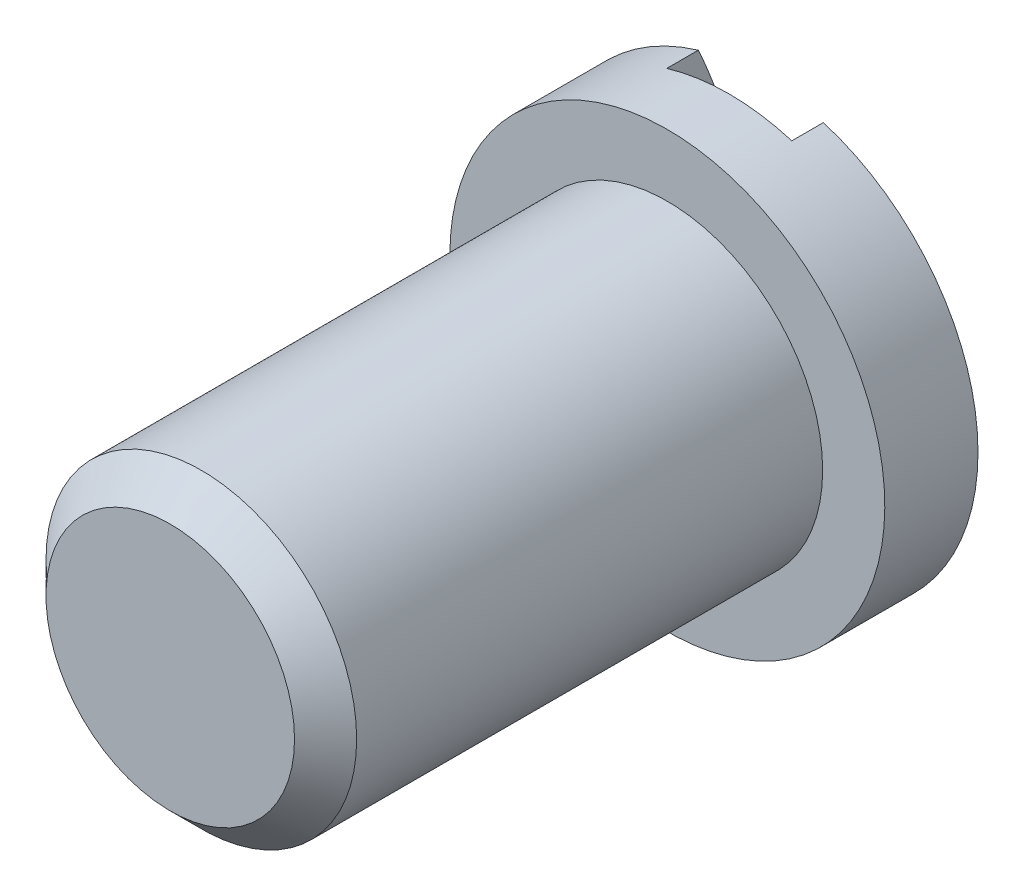
SolidWorks part; units mm, degrees
ref_plane "前视基准面" through (0, 0, 0) normal (0, 0, 1) x (1, 0, 0)
ref_plane "上视基准面" through (0, 0, 0) normal (0, 1, 0) x (1, 0, 0)
ref_plane "右视基准面" through (0, 0, 0) normal (1, 0, 0) x (0, 0, -1)
sketch "草图1" plane through (0, 0, 0) normal (0, 0, 1) x (1, 0, 0)
  circle A0 centre (0, 0) radius 2.5
  dimension "D1" = 5
extrude "凸台-拉伸1" add sketch "草图1" along normal blind 8
cosmetic thread "装饰螺纹线1" parameters "D1"=7.5, "D2"=4
chamfer "倒角2" distance 0.5 angle 45 1 edges at (2.5, 0, 8)
sketch "草图2" plane through (0, 0, 0) normal (0, 0, -1) x (-1, 0, 0)
  circle A0 centre (0, 0) radius 3.5
  dimension "D1" = 7
extrude "凸台-拉伸2" add sketch "草图2" along normal blind 1.5
dome "圆顶1" faces to dome 1 distance 0.8 reverse direction no elliptical dome no face at (-3.5, 0, -1.5) parameters "D1"=0.8
sketch "草图3" plane through (0, 0, 0) normal (0, 1, 0) x (1, 0, 0)
  line L1 (-1.0019, 4.126) -> (1.011, 4.126)
  line L2 (-1.0019, 4.126) -> (-1.0019, 0.9923)
  line L3 (-1.0019, 0.9923) -> (1.011, 0.9923)
  line L4 (1.011, 4.126) -> (1.011, 0.9923)
  line L5 (-1.0019, 4.126) -> (1.011, 0.9923) construction
  line L6 (-1.0019, 0.9923) -> (1.011, 4.126) construction
  point P0 (0.0045, 2.5592)
  point P7 (0, 0)
  point P8 (1.011, 1.5)
extrude "切除-拉伸1" cut sketch "草图3" along normal mid plane 10
